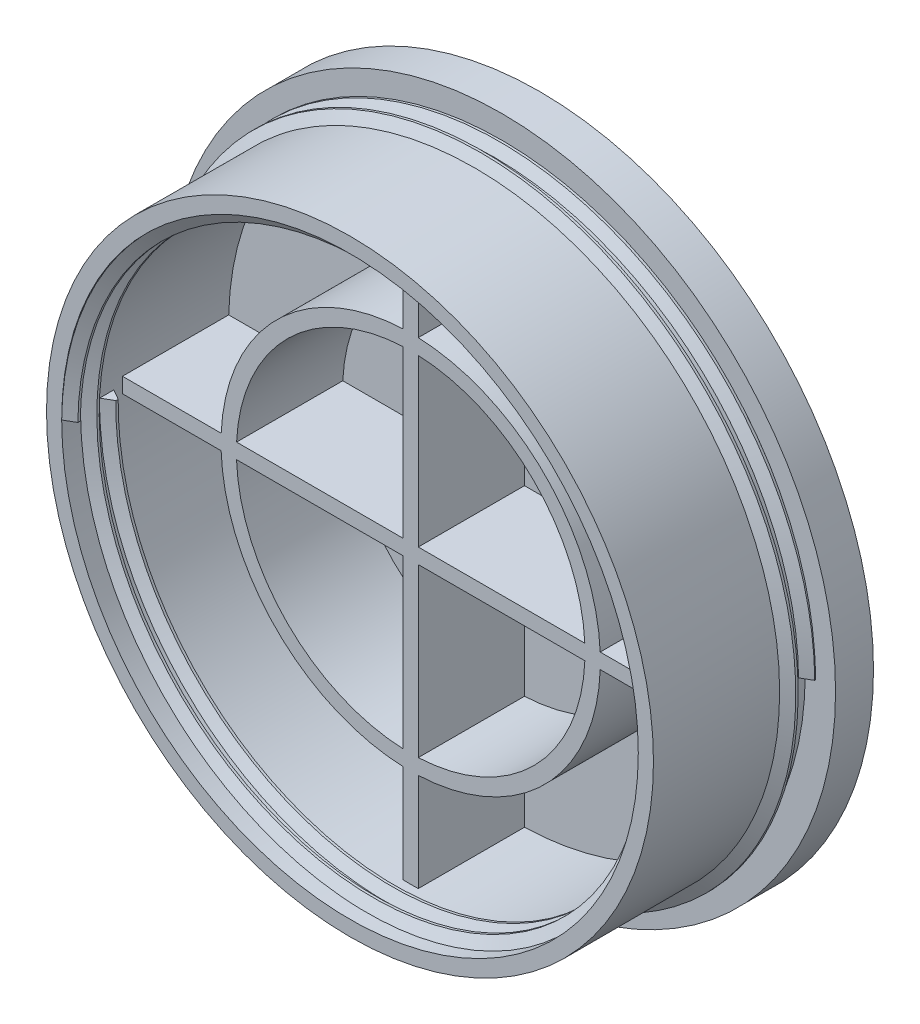
SolidWorks part; units mm, degrees
ref_plane "Front Plane" through (0, 0, 0) normal (0, 0, 1) x (1, 0, 0)
ref_plane "Top Plane" through (0, 0, 0) normal (0, 1, 0) x (1, 0, 0)
ref_plane "Right Plane" through (0, 0, 0) normal (1, 0, 0) x (0, 0, -1)
sketch "Sketch1" plane through (0, 0, 0) normal (0, 0, 1) x (1, 0, 0)
  circle A0 centre (0, 0) radius 44
  dimension "D1" = 88
extrude "Boss-Extrude1" add sketch "Sketch1" along normal blind 5
sketch "Sketch2" plane through (0, 0, 5) normal (0, 0, 1) x (1, 0, 0)
  circle A0 centre (0, 0) radius 40
  dimension "D1" = 80
extrude "Boss-Extrude2" add sketch "Sketch2" along normal blind 5
thread "Thread1" pitch 2.5 method extrude profile "Thread Profile1" start angle 0, offset 1, length 4, pitch 2.5, diameter 80
ref_plane "Plane1" through (40, 0, 4) normal (0, -1, 0) x (1, 0, 0)
sketch "Thread Profile1" plane through (40, 0, 4) normal (0, -1, 0) x (1, 0, 0)
  line L0 (0, 0) -> (0, 2.5) construction
  line L1 (0, 0) -> (1.3532, 0.7812)
  line L2 (1.3532, 0.7812) -> (1.3532, 1.0937)
  line L3 (1.3532, 1.0937) -> (0, 1.875)
  line L4 (1.3532, 0.9375) -> (0, 0.9375) construction
  line L11 (0, 0) -> (0, 1.875)
  point P2 (0, 0)
  dimension "Pitch" = 2.5
  dimension "Profile_Angle" = 60
  dimension "Profile_Land" = 0.3125
  dimension "Profile_Height" = 1.3532
sketch "Sketch5" plane through (0, 0, 0) normal (0, 0, -1) x (-1, 0, 0)
  circle A1 centre (0, 0) radius 44
  circle A2 centre (0, 0) radius 44
  dimension "D1" = 0
extrude "Cut-Extrude1" cut sketch "Sketch5" along normal blind 30 rebuild error yes
sketch "Sketch6" plane through (0, 0, 0) normal (0, 0, -1) x (-1, 0, 0)
  line L0 (0, -44) -> (0, 44) construction
  line L1 (-1, -38) -> (1, -38)
  line L2 (-1, -38) -> (-1, 38)
  line L3 (-1, 38) -> (1, 38)
  line L4 (1, -38) -> (1, 38)
  circle A0 centre (0, 0) radius 44 construction
  dimension "D1" = 2
  dimension "D2" = 1
  dimension "D3" = 6
  dimension "D4" = 6
extrude "Boss-Extrude3" add sketch "Sketch6" along normal blind 10
fillet "Fillet1" radius 10 2 edges at (0, 38, -10) (0, -38, -10)
fillet "Fillet2" radius 5 2 edges at (-1, 0, 0) (1, 0, 0)
sketch "Sketch7" plane through (0, 0, 10) normal (0, 0, 1) x (1, 0, 0)
  circle A0 centre (0, 0) radius 38
  circle A2 centre (0, 0) radius 40
  circle A3 centre (0, 0) radius 40
  dimension "D2" = 2
  dimension "D1" = 0
extrude "Boss-Extrude4" add sketch "Sketch7" along normal blind 15
thread "Thread2" pitch 2.5 method extrude profile "Thread Profile3" start angle 0, offset 0, length 5, pitch 2.5, diameter 76
ref_plane "Plane3" through (-38, 0, 25) normal (0, 1, 0) x (1, 0, 0)
sketch "Thread Profile3" plane through (-38, 0, 25) normal (0, 1, 0) x (1, 0, 0)
  line L0 (0, 0) -> (0, 2.5) construction
  line L1 (0, 0) -> (1.3532, 0.7812)
  line L2 (1.3532, 0.7812) -> (1.3532, 1.0937)
  line L3 (1.3532, 1.0937) -> (0, 1.875)
  line L4 (1.3532, 0.9375) -> (0, 0.9375) construction
  line L11 (0, 0) -> (0, 1.875)
  point P2 (0, 0)
  dimension "Pitch" = 2.5
  dimension "Profile_Angle" = 60
  dimension "Profile_Land" = 0.3125
  dimension "Profile_Height" = 1.3532
sketch "Sketch12" plane through (0, 0, 10) normal (0, 0, 1) x (1, 0, 0)
  line L2 (1, -1) -> (22.9579, -1)
  line L4 (-1, 22.8717) -> (-1, 1)
  line L6 (1, 22.8717) -> (1, 1)
  line L7 (-22.9507, 1) -> (-1, 1)
  line L9 (-22.9579, -1) -> (-1, -1)
  line L11 (1, 1) -> (22.9507, 1)
  line L13 (-1, -1) -> (-1, -23.0372)
  line L14 (1, -1) -> (1, -23.0372)
  circle A1 centre (0, -0.0827) radius 25
  arc A2 (-22.9579, -1) -> (-1, -23.0372) centre (0, -0.0827) ccw
  arc A3 (22.9507, 1) -> (1, 22.8717) centre (0, -0.0827) ccw
  arc A4 (1, -23.0372) -> (22.9579, -1) centre (0, -0.0827) ccw
  arc A5 (-1, 22.8717) -> (-22.9507, 1) centre (0, -0.0827) ccw
  dimension "D5" = 50
  dimension "D6" = 2.0238
extrude "Boss-Extrude10" add sketch "Sketch12" along normal blind 7
sketch "Sketch13" plane through (0, -1, 0) normal (0, -1, 0) x (1, 0, 0)
  line L0 (-1, 17) -> (-22.9579, 17) construction
  line L1 (-39.191, 17) -> (38.5118, 17)
  line L2 (-39.191, 17) -> (-39.191, 10)
  line L3 (-39.191, 10) -> (38.5118, 10)
  line L4 (38.5118, 17) -> (38.5118, 10)
  line L5 (-1, 10) -> (-22.9579, 10) construction
extrude "Boss-Extrude11" add sketch "Sketch13" against normal blind 2
sketch "Sketch14" plane through (1, 0, 0) normal (1, 0, 0) x (0, 0, -1)
  line L0 (-17, 22.8717) -> (-17, 1) construction
  line L1 (-17, -38.4417) -> (-10, -38.4417)
  line L2 (-17, -38.4417) -> (-17, 37.5683)
  line L3 (-17, 37.5683) -> (-10, 37.5683)
  line L4 (-10, -38.4417) -> (-10, 37.5683)
  line L5 (-10, 22.8717) -> (-10, 1) construction
extrude "Boss-Extrude12" add sketch "Sketch14" against normal blind 2 contours L2 L1 L4 L3
sketch "Sketch15" plane through (0, 0, 10) normal (0, 0, 1) x (1, 0, 0)
  line L0 (1, -25.0627) -> (1, -37.9868) construction
  line L1 (37.9868, -1) -> (24.9832, -1) construction
  line L2 (-22.9507, 1) -> (-1, 1)
  line L3 (-1, 1) -> (-1, 22.8717)
  line L4 (-22.9507, 1) -> (-1, 1)
  line L5 (-1, 1) -> (-1, 22.8717)
  line L6 (22.9579, -1) -> (1, -1) construction
  line L7 (1, -1) -> (1, -23.0372) construction
  line L8 (1, 22.8717) -> (1, 1) construction
  line L9 (-1, 24.8973) -> (-1, 37.5683)
  line L10 (-1, 37.5683) -> (1, 37.5683)
  line L11 (1, 37.5683) -> (1, 24.8973)
  line L12 (24.9765, 1) -> (37.9868, 1)
  line L13 (-37.9868, 1) -> (-24.9765, 1)
  line L14 (-1, 24.8973) -> (-1, 37.5683)
  line L15 (-1, 37.5683) -> (1, 37.5683)
  line L16 (1, 37.5683) -> (1, 24.8973)
  line L17 (24.9765, 1) -> (37.9868, 1)
  line L18 (-37.9868, 1) -> (-24.9765, 1)
  line L19 (1, 1) -> (22.9507, 1) construction
  line L20 (-1, -23.0372) -> (-1, -1) construction
  line L21 (-1, -1) -> (-22.9579, -1) construction
  line L22 (-1, -37.9868) -> (-1, -25.0627) construction
  line L23 (-24.9832, -1) -> (-37.9868, -1) construction
  line L24 (1, -25.0627) -> (1, -37.9868)
  line L25 (37.9868, -1) -> (24.9832, -1)
  line L26 (22.9579, -1) -> (1, -1)
  line L27 (1, -1) -> (1, -23.0372)
  line L28 (1, 22.8717) -> (1, 1)
  line L29 (1, 1) -> (22.9507, 1)
  line L30 (-1, -23.0372) -> (-1, -1)
  line L31 (-1, -1) -> (-22.9579, -1)
  line L32 (-1, -37.9868) -> (-1, -25.0627)
  line L33 (-24.9832, -1) -> (-37.9868, -1)
  arc A0 (1, -37.9868) -> (37.9868, -1) centre (0, 0) ccw construction
  arc A1 (-1, 22.8717) -> (-22.9507, 1) centre (0, -0.0827) ccw
  arc A2 (-1, 22.8717) -> (-22.9507, 1) centre (0, -0.0827) ccw
  arc A3 (1, -25.0627) -> (24.9832, -1) centre (0, -0.0827) ccw construction
  arc A4 (1, -23.0372) -> (22.9579, -1) centre (0, -0.0827) ccw construction
  arc A5 (-1, 24.8973) -> (-24.9765, 1) centre (0, -0.0827) ccw
  arc A6 (24.9765, 1) -> (1, 24.8973) centre (0, -0.0827) ccw
  arc A7 (37.9868, 1) -> (-37.9868, 1) centre (0, 0) ccw
  arc A8 (-1, 24.8973) -> (-24.9765, 1) centre (0, -0.0827) ccw
  arc A9 (24.9765, 1) -> (1, 24.8973) centre (0, -0.0827) ccw
  arc A10 (37.9868, 1) -> (-37.9868, 1) centre (0, 0) ccw
  arc A11 (22.9507, 1) -> (1, 22.8717) centre (0, -0.0827) ccw construction
  arc A12 (-22.9579, -1) -> (-1, -23.0372) centre (0, -0.0827) ccw construction
  arc A13 (-37.9868, -1) -> (-1, -37.9868) centre (0, 0) ccw construction
  arc A14 (-24.9832, -1) -> (-1, -25.0627) centre (0, -0.0827) ccw construction
  arc A15 (1, -37.9868) -> (37.9868, -1) centre (0, 0) ccw
  arc A16 (1, -25.0627) -> (24.9832, -1) centre (0, -0.0827) ccw
  arc A17 (1, -23.0372) -> (22.9579, -1) centre (0, -0.0827) ccw
  arc A18 (22.9507, 1) -> (1, 22.8717) centre (0, -0.0827) ccw
  arc A19 (-22.9579, -1) -> (-1, -23.0372) centre (0, -0.0827) ccw
  arc A20 (-37.9868, -1) -> (-1, -37.9868) centre (0, 0) ccw
  arc A21 (-24.9832, -1) -> (-1, -25.0627) centre (0, -0.0827) ccw
  dimension "D1" = 0
  dimension "D2" = 0
extrude "Cut-Extrude2" cut sketch "Sketch15" against normal blind 7
